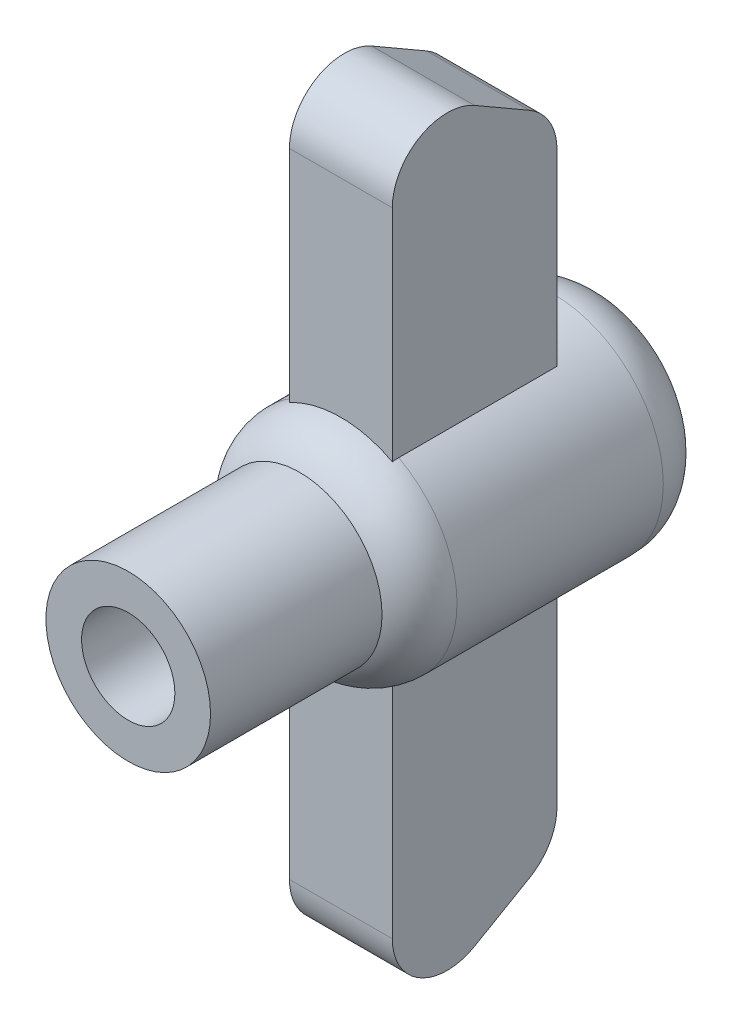
SolidWorks part; units mm, degrees
material "PE Low/Medium Density"
ref_plane "Plano frontal" through (0, 0, 0) normal (0, 0, 1) x (1, 0, 0)
ref_plane "Plano superior" through (0, 0, 0) normal (0, 1, 0) x (1, 0, 0)
ref_plane "Plano direito" through (0, 0, 0) normal (1, 0, 0) x (0, 0, -1)
sketch "Sketch2" plane through (0, 0, 0) normal (0, 1, 0) x (1, 0, 0)
  line L0 (0, 0) -> (0, 35)
  line L1 (0, 35) -> (-8, 35)
  line L2 (-8, 35) -> (-8, 27.5)
  line L3 (-8, 27.5) -> (-18, 27.5)
  line L4 (-18, 27.5) -> (-23.5, 15.5)
  line L6 (-6, 12.5) -> (-6, 0)
  line L7 (-6, 0) -> (0, 0)
  line L8 (-8, 27.5) -> (-8, 12.5)
  line L9 (-8, 12.5) -> (-8, 15.5)
  line L10 (-8, 15.5) -> (-23.5, 15.5)
  line L11 (-6, 12.5) -> (-8, 12.5)
  dimension "D1" = 35
  dimension "D2" = 15
  dimension "D3" = 7.5
  dimension "D4" = 12
  dimension "D5" = 6
  dimension "D6" = 18
  dimension "D7" = 10
  dimension "D8" = 17.5
revolve "Revolve1" add sketch "Sketch2" angle 360 about L0 region at (-3.7059, 0, -18.6029)
sketch "Sketch4" plane through (0, 0, 0) normal (0, 1, 0) x (1, 0, 0)
  line L0 (-3.75, 27.5) -> (-3.75, 15.5)
  line L1 (3.75, 15.5) -> (-3.75, 15.5)
  line L3 (3.75, 15.5) -> (3.75, 27.5)
  line L5 (-3.75, 27.5) -> (3.75, 27.5)
  line L8 (-8, 27.5) -> (-18, 27.5) construction
  line L9 (-8, 15.5) -> (-23.5, 15.5) construction
  point P0 (0, 27.5)
  dimension "D2" = 7.5
extrude "Boss-Extrude2" add sketch "Sketch4" along normal mid plane 60
sketch "Sketch5" plane through (3.75, 0, 0) normal (1, 0, 0) x (0, 0, -1)
  line L0 (15.5, 30) -> (27.5, 23.0718)
  line L1 (27.5, 7.0666) -> (27.5, 30) construction
  line L2 (27.5, 23.0718) -> (27.5, 30)
  line L3 (27.5, 30) -> (15.5, 30)
  line L5 (15.5, 30) -> (15.5, 7.0666) construction
  dimension "D1" = 60
extrude "Cut-Extrude1" cut sketch "Sketch5" against normal through all both and the other way through all
sketch "Sketch6" plane through (3.75, 0, 0) normal (1, 0, 0) x (0, 0, -1)
  line L0 (15.5, -30) -> (27.5, -23.0718)
  line L1 (27.5, -30) -> (27.5, -7.0666) construction
  line L2 (27.5, -23.0718) -> (27.5, -30)
  line L3 (27.5, -30) -> (15.5, -30)
  line L5 (15.5, -7.0666) -> (15.5, -30) construction
  dimension "D1" = 60
extrude "Cut-Extrude2" cut sketch "Sketch6" against normal through all both and the other way through all
hole_wizard "M8 Tapped Hole2" positions "Sketch7" profile "Sketch8" tap size "M8" standard "ISO"
sketch "Sketch7" plane through (0, 0, 0) normal (0, 0, 1) x (1, 0, 0)
  point P0 (0, 0)
sketch "Sketch8" plane through (0, 0, 0) normal (1, 0, 0) x (0, -1, 0)
  line L0 (0, 0) -> (0, 22.0429)
  line L1 (0, 22.0429) -> (3.4, 20)
  line L2 (3.4, 20) -> (3.4, 0)
  line L5 (3.4, 0) -> (0, 0)
  line L10 (0, 22.0429) -> (-3.4, 20) construction
  line L11 (0, -6.35) -> (0, 107.95) construction
  dimension "Tap Drill Dia." = 6.8
  dimension "Tap Drill Depth" = 20
  dimension "Drill Angle" = 118
cosmetic thread "Hole Thread2" parameters "D1"=7.4, "D2"=8
fillet "Fillet1" radius 4 4 edges at (0, -23.0718, -27.5) (0, 23.0718, -27.5) (0, 30, -15.5) (0, -30, -15.5)
fillet "Fillet2" radius 4 2 edges at (8, 0, -35) (8, 0, -12.5)
